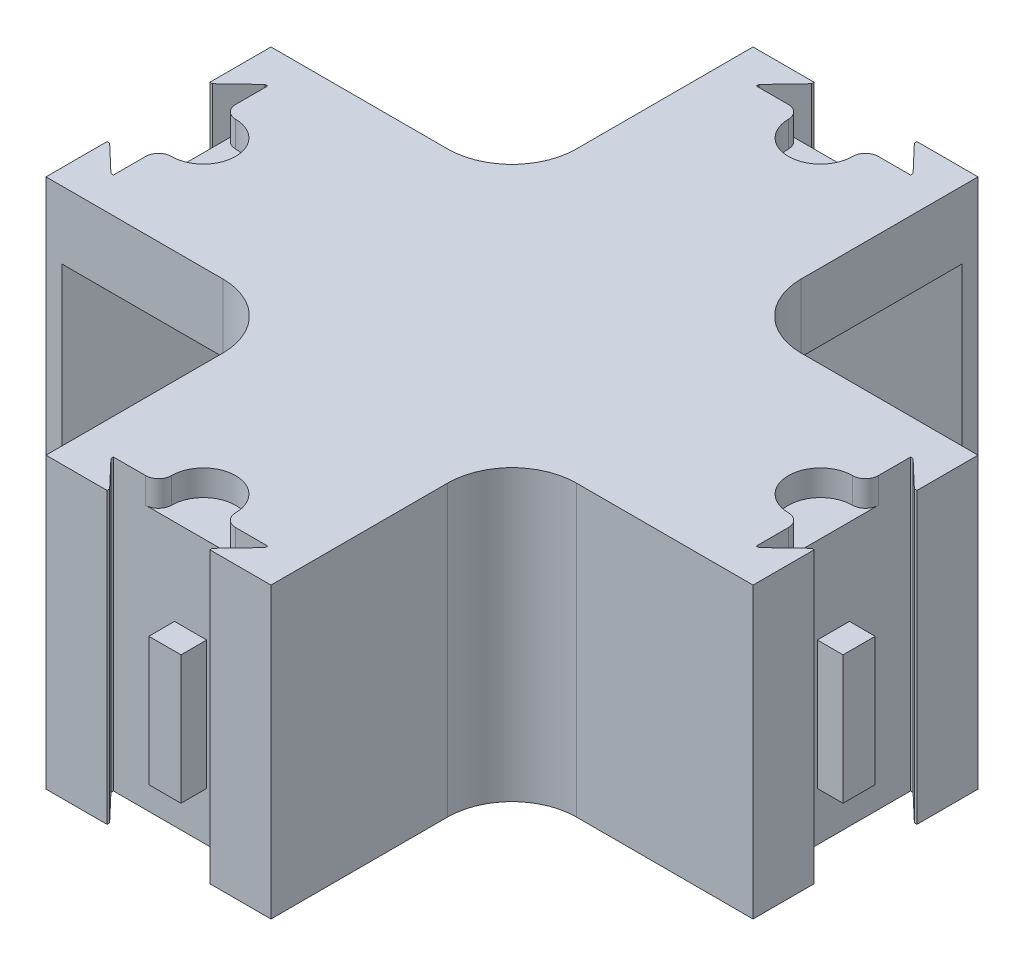
SolidWorks part; units mm, degrees
ref_plane "Front Plane" through (0, 0, 0) normal (0, 0, 1) x (1, 0, 0)
ref_plane "Top Plane" through (0, 0, 0) normal (0, 1, 0) x (1, 0, 0)
ref_plane "Right Plane" through (0, 0, 0) normal (1, 0, 0) x (0, 0, -1)
sketch "Sketch1" plane through (0, 0, 0) normal (0, 1, 0) x (1, 0, 0)
  line L0 (17.4176, 71.3548) -> (17.4176, 43.8548)
  line L1 (17.4176, -38.6452) -> (-17.5824, -38.6452)
  line L2 (-17.5824, 43.8548) -> (-17.5824, 71.3548)
  line L3 (-17.5824, 71.3548) -> (17.4176, 71.3548)
  line L4 (-17.5824, -38.6452) -> (-17.5824, -11.1452)
  line L5 (-27.5824, -1.1452) -> (-55.0824, -1.1452)
  line L6 (-55.0824, -1.1452) -> (-55.0824, 33.8548)
  line L7 (-55.0824, 33.8548) -> (-27.5824, 33.8548)
  line L8 (-17.5824, 33.8548) -> (17.4176, 33.8548)
  line L9 (27.4176, 33.8548) -> (54.9176, 33.8548)
  line L10 (54.9176, 33.8548) -> (54.9176, -1.1452)
  line L11 (54.9176, -1.1452) -> (27.4176, -1.1452)
  line L12 (17.4176, -1.1452) -> (-17.5824, 33.8548)
  line L13 (17.4176, 33.8548) -> (-17.5824, -1.1452)
  line L14 (-0.0824, 16.3548) -> (27.6715, 44.1087)
  line L15 (10.1706, 61.6096) -> (45.1724, 26.6079)
  line L16 (-45.3373, 6.1018) -> (-10.3355, -28.9)
  line L17 (17.4176, 68.8566) -> (-52.5842, -1.1452)
  line L18 (52.4193, 33.8548) -> (-17.5824, -36.147)
  line L19 (17.4176, -38.6452) -> (17.4176, -11.1452)
  arc A0 (-27.5824, 33.8548) -> (-17.5824, 43.8548) centre (-27.5824, 43.8548) ccw
  arc A1 (-17.5824, -11.1452) -> (-27.5824, -1.1452) centre (-27.5824, -11.1452) ccw
  arc A2 (17.4176, 43.8548) -> (27.4176, 33.8548) centre (27.4176, 43.8548) ccw
  arc A3 (27.4176, -1.1452) -> (17.4176, -11.1452) centre (27.4176, -11.1452) ccw
  dimension "D1" = 10
  dimension "D4" = 10
  dimension "D5" = 10
  dimension "D6" = 10
  dimension "D2" = 39.25
  dimension "D3" = 49.5
extrude "Boss-Extrude1" add sketch "Sketch1" along normal blind 45 contours A0 L7 L6 L5 L17 L0 L3 L2 | L16 L17 L5 | A2 L0 L15 L17 L16 L5 A1 L4 L18 L9 L13 L12 L8 | L13 L8 L12 | L0 L17 L15 | L18 L9 L15 | A3 L11 L10 L9 L18 L4 L1 L19 | L18 L16 L4 region at (16.3922, 0, -70.1057) region at (15.0019, 0, -61.6096) region at (-0.0824, 0, -28.0215) region at (-0.0824, 0, -15.2389) region at (-45.3373, 0, -1.2705) region at (45.1724, 0, -31.4392) region at (53.6684, 0, -32.8295) region at (-15.1668, 0, 28.9)
extrude "Cut-Extrude1" cut sketch "Sketch1<3>" along normal blind 34.5 contours L16 L17 L5 | A2 L0 L15 L17 L16 L5 A1 L4 L18 L9 L13 L12 L8 | L18 L16 L4 | L13 L8 L12 | L0 L17 L15 | L18 L9 L15 region at (15.0019, 0, -61.6096) region at (-0.0824, 0, -28.0215) region at (-0.0824, 0, -15.2389) region at (-45.3373, 0, -1.2705) region at (45.1724, 0, -31.4392) region at (-15.1668, 0, 28.9)
sketch "Sketch1<3>" plane through (0, 0, 0) normal (0, 1, 0) x (1, 0, 0) same geometry as "Sketch1"
ref_plane "Plane1" through (0, 0, -16.3548) normal (0, 0, 1) x (1, 0, 0)
sketch "Sketch3" plane through (0, 45, 0) normal (0, 1, 0) x (1, 0, 0)
  line L0 (-55.0824, 8.3548) -> (-55.0824, 24.3548)
  line L1 (-55.0824, -1.1452) -> (-55.0824, 33.8548) construction
  line L2 (-55.0824, 24.3548) -> (-54.6824, 24.3548)
  line L3 (-55.0824, 16.3548) -> (-50.0824, 16.3548)
  line L4 (-24.75, 16.3548) -> (24.75, 16.3548) construction
  line L5 (-50.0824, 4.3548) -> (-50.0824, 28.3548)
  line L6 (-50.0824, 28.3548) -> (-50.4824, 28.3548)
  line L7 (-50.4824, 28.3548) -> (-54.6824, 24.3548)
  line L8 (-50.0824, 4.3548) -> (-50.4824, 4.3548)
  line L9 (-55.0824, 8.3548) -> (-54.6824, 8.3548)
  line L10 (-50.4824, 4.3548) -> (-54.6824, 8.3548)
  line L11 (-50.0824, 16.3548) -> (-48.0824, 16.3548)
  line L14 (-48.0824, 11.3548) -> (-48.0824, 9.3548)
  circle A0 centre (-48.0824, 16.3548) radius 2
  arc A1 (-48.0824, 11.3548) -> (-48.0824, 21.3548) centre (-48.0824, 16.3548) ccw
  circle A2 centre (-48.0824, 9.3548) radius 2
  circle A3 centre (-48.0824, 23.3548) radius 2
  line M27 (-55.0824, 33.8548) -> (-55.0824, -1.1452)
  dimension "D1" = 0.4
  dimension "D5" = 5
  dimension "D6" = 4
  dimension "D2" = 0.4
  dimension "D3" = 24
  dimension "D4" = 16
ref_plane "Plane3" through (-0.0824, 0, 0) normal (1, 0, 0) x (0, 0, -1)
ref_axis "Axis1" through (-0.0824, -2.25, -16.3548) along (0, 1, 0)
ref_axis "Axis2" through (20.3465, 45, -36.7837) along (-0.7071, 0, 0.7071)
extrude "Cut-Extrude2" cut sketch "Sketch3" against normal through all contours L10 L8 L5 L3 L0 L9 | L6 L7 L2 L3 L5 M27 region at (-52.3912, 45, -11.2668) region at (-52.3912, 45, -21.4428)
extrude "Cut-Extrude3" cut sketch "Sketch3<3>" against normal blind 4 contours A1 A3 L5 A0 A2 | A0 region at (-49.9259, 45, -19.8548) region at (-48.0824, 45, -18.2982)
sketch "Sketch3<3>" plane through (0, 45, 0) normal (0, 1, 0) x (1, 0, 0) same geometry as "Sketch3"
pattern_circular "CirPattern1" count 4 over 360 about axis through (-0.0824, -2.25, -16.3548) along (0, 1, 0) of "Cut-Extrude3", "Cut-Extrude2"
sketch "Sketch5" plane through (0, 0, 33.6452) normal (0, 0, 1) x (1, 0, 0)
  line L0 (-0.0824, 45) -> (-0.0824, 44.05)
  line L1 (-0.0824, -2.25) -> (-0.0824, 47.25) construction
  line L2 (20.3465, 45) -> (-20.5114, 45) construction
  line L3 (-0.0824, -24.75) -> (-0.0824, 24.75) construction
  line L4 (-0.0824, 45) -> (-0.0824, 35.6)
  line L5 (-0.0824, 31.6) -> (-0.0824, 27.6)
  line L6 (-2.5824, 27.6) -> (2.4176, 27.6)
  line L7 (2.4176, 27.6) -> (2.4176, 7.6)
  line L8 (-2.5824, 27.6) -> (-2.5824, 7.6)
  line L9 (2.4176, 7.6) -> (-2.5824, 7.6)
  circle A0 centre (-0.0824, 35.6) radius 4
  dimension "D1" = 9.4
  dimension "D3" = 8
  dimension "D2" = 4
  dimension "D4" = 2.5
  dimension "D5" = 20
extrude "Boss-Extrude2" add sketch "Sketch5" along normal blind 4 contours L9 L7 L6 L8 region at (-0.0824, 17.6, 33.6452)
pattern_circular "CirPattern2" count 4 over 360 about axis through (-0.0824, -2.25, -16.3548) along (0, 1, 0) of "Boss-Extrude2"
